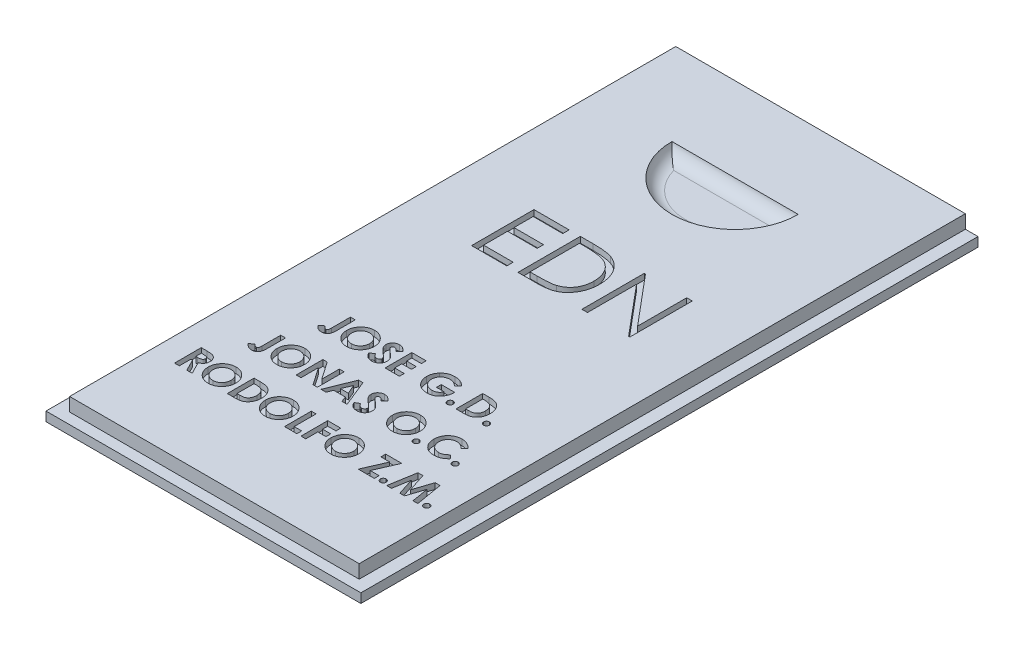
SolidWorks part; units mm, degrees
ref_plane "Front Plane" through (0, 0, 0) normal (0, 0, 1) x (1, 0, 0)
ref_plane "Top Plane" through (0, 0, 0) normal (0, 1, 0) x (1, 0, 0)
ref_plane "Right Plane" through (0, 0, 0) normal (1, 0, 0) x (0, 0, -1)
sketch "Croquis1" plane through (0, 0, 0) normal (0, 0, 1) x (1, 0, 0)
  line L0 (-18.7, 0) -> (-18.7, 1.1)
  line L1 (-18.7, 1.1) -> (-17.2, 1.1)
  line L2 (-17.2, 1.1) -> (-17.2, 2.7)
  line L3 (-17.2, 2.7) -> (17.2, 2.7)
  line L4 (17.2, 2.7) -> (17.2, 1.1)
  line L5 (17.2, 1.1) -> (18.7, 1.1)
  line L6 (18.7, 1.1) -> (18.7, 0)
  line L7 (18.7, 0) -> (-18.7, 0)
  point P2 (0, 0)
  dimension "D1" = 1.5
  dimension "D2" = 1.5
  dimension "D3" = 37.4
  dimension "D4" = 1.1
  dimension "D5" = 1.1
  dimension "D6" = 1.6
extrude "Saliente-Extruir1" add sketch "Croquis1" along normal blind 72
sketch "Croquis2" plane through (0, 0, 72) normal (0, 0, 1) x (1, 0, 0)
  line L0 (18.7, 1.1) -> (18.7, 0)
  line L1 (18.7, 0) -> (-18.7, 0)
  line L2 (-18.7, 0) -> (-18.7, 1.1)
  line L3 (-18.7, 1.1) -> (18.7, 1.1)
extrude "Saliente-Extruir2" add sketch "Croquis2" along normal blind 1.3
sketch "Croquis3" plane through (0, 2.7, 0) normal (0, 1, 0) x (1, 0, 0)
  line L0 (-7.65, -10) -> (7.35, -10)
  line L1 (17.2, 0) -> (-17.2, 0) construction
  line L2 (-17.2, -72) -> (-17.2, 0) construction
  arc A0 (-7.65, -10) -> (7.35, -10) centre (-0.15, -10) ccw
  dimension "D1" = 15
  dimension "D2" = 10
  dimension "D3" = 17.05
extrude "Cortar-Extruir1" cut sketch "Croquis3" against normal blind 1.3
fillet "Redondeo4" radius 1.6 2 edges at (-0.15, 1.4, 10) (-0.15, 1.4, 17.5)
sketch "Croquis5" plane through (0, 2.7, 0) normal (0, 1, 0) x (1, 0, 0)
  line L0 (-11.2577, -32.6059) -> (12.3755, -32.6059) construction
  line L1 (-15.2, -50.3328) -> (16.3177, -50.3328) construction
  line L2 (-15.2, -56.3328) -> (16.3177, -56.3328) construction
  line L3 (-15.2, -62.3328) -> (16.3177, -62.3328) construction
  line L4 (17.2, 0) -> (-17.2, 0) construction
  line L5 (-17.2, -72) -> (-17.2, 0) construction
  text T0 "EDN" font "Century Gothic" height in points 28
  text T1 "JOSE G.D." font "Century Gothic" height in points 12
  text T2 "JONAS O.C." font "Century Gothic" height in points 12
  text T3 "RODOLFO Z.M." font "Century Gothic" height in points 12
  point P8 (0.5589, -50.3328)
  point P11 (0.5589, -56.3328)
  dimension "D1" = 32.6059
  dimension "D2" = 6
  dimension "D3" = 6
  dimension "D4" = 50.3328
  dimension "D5" = 2
  dimension "D6" = 2
  dimension "D7" = 2
extrude "Cortar-Extruir5" cut sketch "Croquis5" against normal blind 0.7
sketch "Croquis6" plane through (0, 0, 0) normal (0, -1, 0) x (1, 0, 0)
  line L0 (2.2, 1.9) -> (2.2, 0.9)
  line L1 (2.2, 1.9) -> (-2.2, 1.9)
  line L2 (2.2, 0.9) -> (-2.2, 0.9)
  line L3 (-2.2, 1.9) -> (-2.2, 0.9)
  line L4 (2.2, 1.9) -> (-2.2, 0.9) construction
  line L5 (2.2, 0.9) -> (-2.2, 1.9) construction
  line L6 (-18.7, 0) -> (18.7, 0) construction
  point P1 (0, 1.4)
  dimension "D1" = 0.9
  dimension "D2" = 1
  dimension "D3" = 4.4
extrude "Saliente-Extruir3" add sketch "Croquis6" along normal blind 0.35
fillet "Redondeo11" radius 0.3 4 edges at (2.2, -0.35, 1.4) (0, -0.35, 0.9) (-2.2, -0.35, 1.4) (0, -0.35, 1.9)
